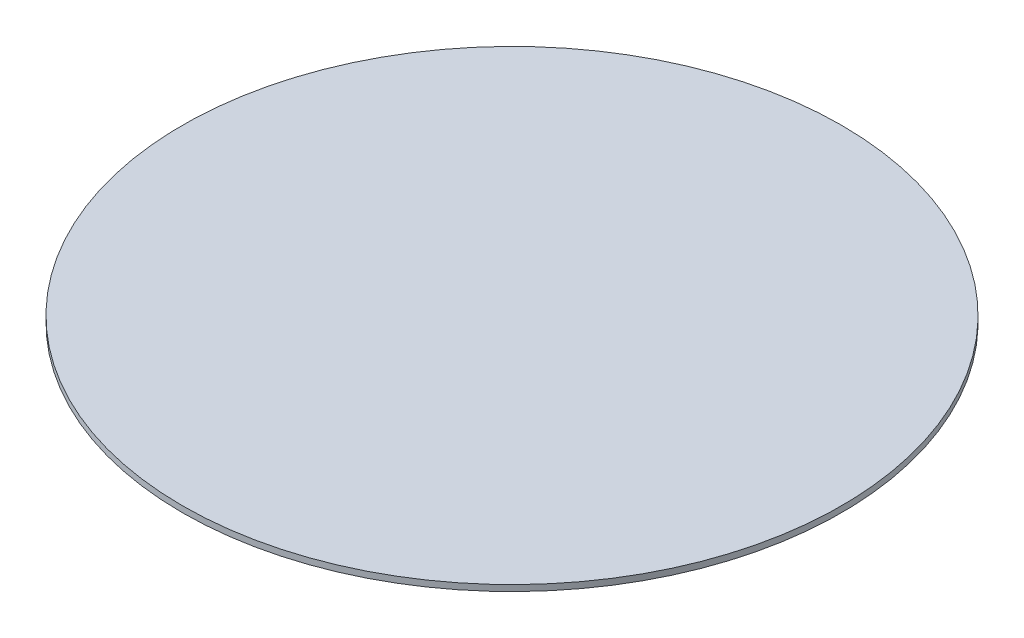
SolidWorks part; units mm, degrees
ref_plane "Front Plane" through (0, 0, 0) normal (0, 0, 1) x (1, 0, 0)
ref_plane "Top Plane" through (0, 0, 0) normal (0, 1, 0) x (1, 0, 0)
ref_plane "Right Plane" through (0, 0, 0) normal (1, 0, 0) x (0, 0, -1)
sketch "Sketch1" plane through (0, 0, 0) normal (0, 1, 0) x (1, 0, 0)
  circle A0 centre (0, 0) radius 40
  dimension "D1" = 80
base flange "Base-Flange1" sketch "Sketch1" thickness 0.7366 reverse thickness direction no parameters "D1"=0.7366
sketch "Bend-Lines1" plane through (0, 0, 0) normal (0, 1, 0) x (1, 0, 0)
sketch "Bounding-Box1" plane through (0, 0, 0) normal (0, 1, 0) x (1, 0, 0)
sheet metal parameters "Sheet-Metal1" thickness 0.7366 parameters "D1"=0.7366
flat pattern "Flat-Pattern1" [suppressed]
sketch "Bend-Lines2" plane through (0, 0, 0) normal (0, 1, 0) x (1, 0, 0)
sketch "Bounding-Box2" [suppressed] plane through (0, 0, 0) normal (0, 1, 0) x (1, 0, 0)
